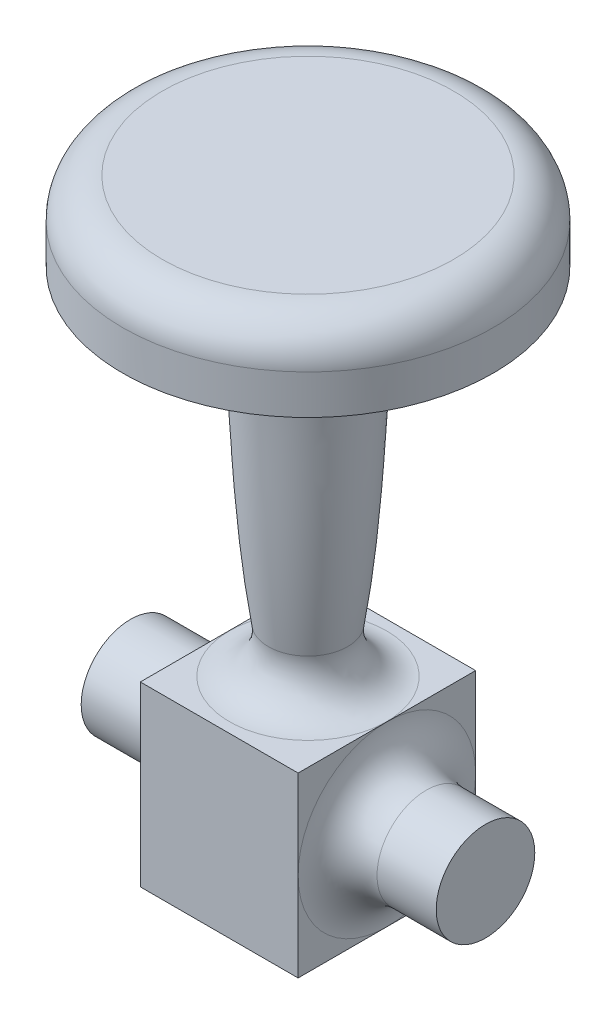
SolidWorks part; units mm, degrees
ref_plane "Front Plane" through (0, 0, 0) normal (0, 0, 1) x (1, 0, 0)
ref_plane "Top Plane" through (0, 0, 0) normal (0, 1, 0) x (1, 0, 0)
ref_plane "Right Plane" through (0, 0, 0) normal (1, 0, 0) x (0, 0, -1)
sketch "Sketch2" plane through (0, 0, 0) normal (1, 0, 0) x (0, 0, -1)
  line L1 (0, 0) -> (11.43, 0)
  line L2 (0, 0) -> (0, 11.43)
  line L3 (0, 11.43) -> (11.43, 11.43)
  line L4 (11.43, 0) -> (11.43, 11.43)
  dimension "D1" = 11.43
  dimension "D2" = 11.43
extrude "central box" add sketch "Sketch2" along normal blind 10.16
ref_point "center for extrusion of nibbles"
sketch "Sketch4" plane through (10.16, 0, 0) normal (1, 0, 0) x (0, 0, -1)
  circle A0 centre (5.715, 5.715) radius 3.175
  dimension "D1" = 6.35
extrude "nibbles" add sketch "Sketch4" along normal blind 6.35 and the other way offset from surface (16.51 mm away) 6.35 other way up to face at (0, 5.715, -5.715)
ref_point "stick extrusion spot"
ref_plane "stick drawin' plane" through (0, 0, -5.715) normal (0, 0, 1) x (1, 0, 0)
sketch "Sketch6" plane through (0, 0, -5.715) normal (0, 0, 1) x (1, 0, 0)
  line L0 (5.08, 11.43) -> (5.08, 39.37)
  line L1 (5.08, 39.37) -> (17.0076, 39.37)
  line L2 (17.0076, 39.37) -> (17.0076, 34.29)
  line L3 (5.08, 11.43) -> (7.112, 11.43)
  spline S0 degree 3 poles (17.0076, 34.29) (5.9591, 41.9441) (10.419, 27.6452) (7.112, 11.43) knots 0 0 0 0 1 1 1 1
  dimension "D1" = 2.032
  dimension "D2" = 27.94
  dimension "D3" = 5.08
revolve "stick" add sketch "Sketch6" angle 360 about L0
fillet "yay, rounded" radius 2.54 4 edges at (5.08, 11.43, -7.747) (5.08, 39.37, -17.6426) (10.16, 5.715, -2.54) (0, 5.715, -2.54)
